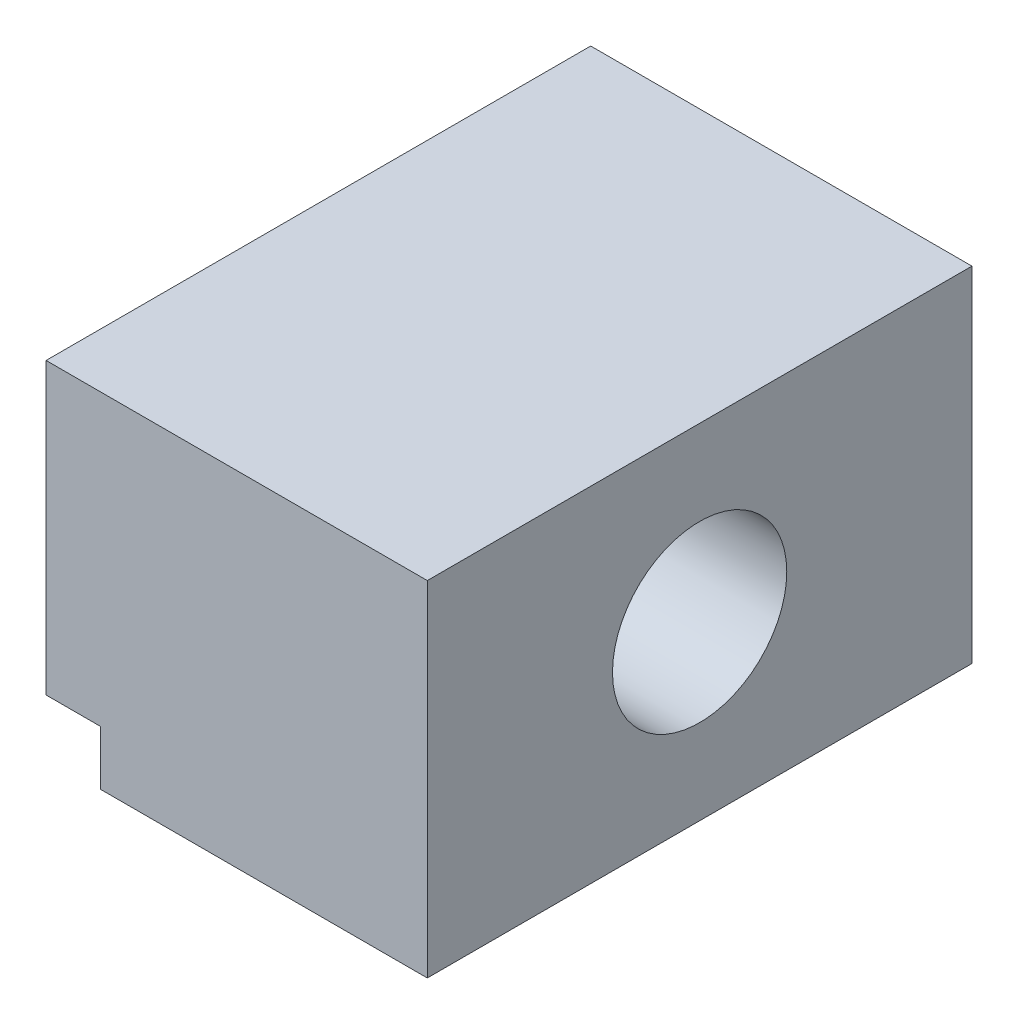
SolidWorks part; units mm, degrees
ref_plane "Front Plane" through (0, 0, 0) normal (0, 0, 1) x (1, 0, 0)
ref_plane "Top Plane" through (0, 0, 0) normal (0, 1, 0) x (1, 0, 0)
ref_plane "Right Plane" through (0, 0, 0) normal (1, 0, 0) x (0, 0, -1)
sketch "Sketch1" plane through (0, 0, 0) normal (0, 1, 0) x (1, 0, 0)
  line L1 (-3, 2.5) -> (3, 2.5)
  line L2 (-3, 2.5) -> (-3, -2.5)
  line L3 (-3, -2.5) -> (3, -2.5)
  line L4 (3, 2.5) -> (3, -2.5)
  line L5 (-3, 2.5) -> (3, -2.5) construction
  line L6 (-3, -2.5) -> (3, 2.5) construction
  point P0 (0, 0)
  dimension "D1" = 6
  dimension "D2" = 5
extrude "Boss-Extrude1" add sketch "Sketch1" along normal blind 0.5
sketch "Sketch2" plane through (0, 0.5, 0) normal (0, 1, 0) x (1, 0, 0)
  line L1 (-3.5, -2.5) -> (3.5, -2.5)
  line L2 (-3.5, -2.5) -> (-3.5, 2.5)
  line L3 (-3.5, 2.5) -> (3.5, 2.5)
  line L4 (3.5, -2.5) -> (3.5, 2.5)
  line L5 (-3.5, -2.5) -> (3.5, 2.5) construction
  line L6 (-3.5, 2.5) -> (3.5, -2.5) construction
  point P0 (0, 0)
  dimension "D1" = 5
  dimension "D2" = 7
extrude "Boss-Extrude2" add sketch "Sketch2" along normal offset from surface (2.66 mm away) 3.16 up to face at (0, 0, 0)
sketch "Sketch3" plane through (-3.5, 0, 0) normal (-1, 0, 0) x (0, 0, 1)
  line L0 (0, 0) -> (0, 3.16) construction
  line L1 (-2.5, 3.16) -> (2.5, 3.16) construction
  circle A0 centre (0, 1.58) radius 0.8
  dimension "D2" = 1.6
  dimension "D1" = 1.58
extrude "Cut-Extrude1" cut sketch "Sketch3" against normal through all
chamfer "Chamfer1" distance 0.5 angle 45 2 edges at (3.5, 1.58, 0.8) (-3.5, 1.58, 0.8)
sketch "Sketch4" plane through (0, 3.16, 0) normal (0, 1, 0) x (1, 0, 0)
  line L0 (3.5, 2.5) -> (-3.5, 2.5) construction
  line L1 (0, 2.5) -> (3.5, 2.5)
  line L2 (0, 2.5) -> (0, -2.5)
  line L3 (0, -2.5) -> (3.5, -2.5)
  line L4 (3.5, 2.5) -> (3.5, -2.5)
extrude "Cut-Extrude2" cut sketch "Sketch4" against normal through all both and the other way through all
